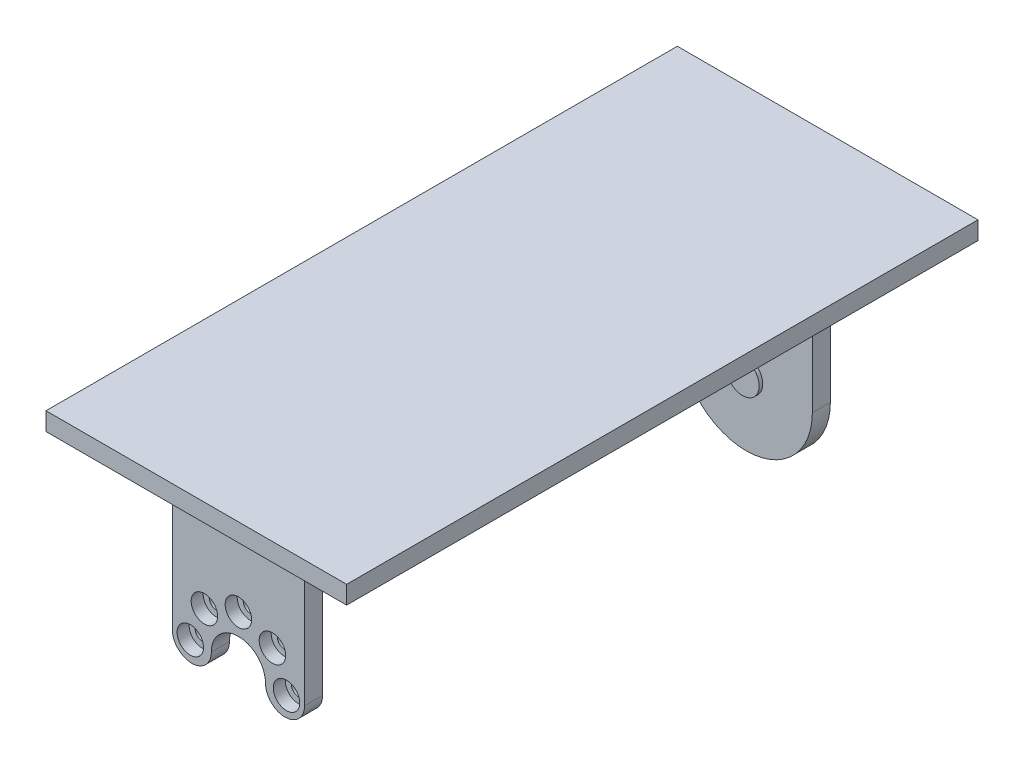
SolidWorks part; units mm, degrees
ref_plane "Plano frontal" through (0, 0, 0) normal (0, 0, 1) x (1, 0, 0)
ref_plane "Plano superior" through (0, 0, 0) normal (0, 1, 0) x (1, 0, 0)
ref_plane "Plano direito" through (0, 0, 0) normal (1, 0, 0) x (0, 0, -1)
other "Centro da massa"
sketch "Esboço1" plane through (0, 0, 0) normal (0, 0, 1) x (1, 0, 0)
  line L0 (11, 0) -> (11, 25)
  line L1 (11, 25) -> (-11, 25)
  line L2 (-11, 25) -> (-11, 0)
  arc A3 (11, 0) -> (4.5, 0) centre (7.75, 0) cw
  arc A8 (4.5, 0) -> (-4.5, 0) centre (0, 0) ccw
  arc A10 (-4.5, 0) -> (-11, 0) centre (-7.75, 0) cw
  dimension "D1" = 25
extrude "Ressalto-extrusão1" add sketch "Esboço1" along normal blind 3
sketch "Esboço2" plane through (0, 25, 0) normal (0, 1, 0) x (1, 0, 0)
  line L1 (-25, -10) -> (25, -10)
  line L2 (-25, -10) -> (-25, 95)
  line L3 (-25, 95) -> (25, 95)
  line L4 (25, -10) -> (25, 95)
  line L5 (11, -3) -> (-11, -3) construction
  point P7 (0, -3)
  point P8 (0, -10)
  dimension "D1" = 105
  dimension "D2" = 50
  dimension "D3" = 7
extrude "Ressalto-extrusão2" add sketch "Esboço2" along normal blind 3
ref_plane "Plano1" through (0, 0, -81.45) normal (0, 0, -1) x (-1, 0, 0)
sketch "Esboço3" plane through (0, 0, -81.45) normal (0, 0, -1) x (-1, 0, 0)
  line L1 (-11, 0) -> (-11, 25)
  line L2 (-11, 25) -> (11, 25)
  line L3 (11, 25) -> (11, 0)
  arc A0 (-11, 0) -> (11, 0) centre (0, 0) ccw
  dimension "D1" = 22
extrude "Ressalto-extrusão3" add sketch "Esboço3" along normal blind 3
hole_wizard "Rebaixo para SHCS M21" positions "Esboço4" profile "Esboço5" counterbore size "M2" standard "Ansi Metric" end condition up to next
sketch "Esboço4" plane through (0, 0, 3) normal (0, 0, 1) x (1, 0, 0)
  arc A0 (8.8, 0) -> (7.2, 0) centre (8, 0) ccw construction
  point P0 (8, 0)
sketch "Esboço5" plane through (8, 0, 3) normal (1, 0, 0) x (0, -1, 0)
  line L0 (0, 0) -> (0, 3)
  line L1 (0, 3) -> (1.2, 3)
  line L3 (1.2, 3) -> (1.2, 2)
  line L4 (1.2, 2) -> (2.2, 2)
  line L5 (2.2, 2) -> (2.2, 0)
  line L7 (2.2, 0) -> (0, 0)
  line L11 (0, -6.35) -> (0, 107.95) construction
  dimension "Thru Hole Dia." = 2.4
  dimension "Thru Hole Depth" = 3
  dimension "C'Bore Dia." = 4.4
  dimension "C'Bore Depth" = 2
pattern_circular "PadrãoCircular1" count 5 over 180 about axis through (0, 0, 3) along (0, 0, -1) of "Rebaixo para SHCS M21" reverse direction yes
sketch "Esboço6" plane through (0, 0, 0) normal (1, 0, 0) x (0, 0, -1)
  line L0 (-10, 25) -> (-3, 25) construction
  line L3 (-3, 25) -> (-3, 18) construction
  line L4 (-3, 0) -> (-3, 25) construction
  line L5 (-3, 18) -> (-10, 25)
rib "Nervura1" sketch "Esboço6" sketch "Esboço6" thickness 15 extrusion direction parallel to sketch draft on no parameters "D1"=15
sketch "Esboço7" plane through (0, 0, 3) normal (0, 0, 1) x (1, 0, 0)
  line L0 (-7.5, 25) -> (7.5, 25) construction
  line L1 (-5, 25) -> (5, 25)
  line L2 (-5, 25) -> (-5, 18)
  line L3 (-5, 18) -> (5, 18)
  line L4 (5, 25) -> (5, 18)
  line L5 (7.5, 18) -> (-7.5, 18) construction
  point P8 (0, 18)
  point P9 (0, 18)
  dimension "D1" = 10
extrude "Corte-extrusão1" cut sketch "Esboço7" along normal up to surface (7 mm away) up to face at (0, 21.5, 6.5)
sketch "Esboço8" plane through (0, 0, 0) normal (1, 0, 0) x (0, 0, -1)
  line L0 (0, 18) -> (7, 25)
  line L1 (0, 0) -> (0, 25) construction
  line L2 (-10, 25) -> (95, 25) construction
  line L5 (-10, 25) -> (-3, 18) construction
rib "Nervura7" sketch "Esboço8" sketch "Esboço8" thickness 15 extrusion direction parallel to sketch draft on no parameters "D1"=15
sketch "Esboço9" plane through (0, 0, 0) normal (0, 0, -1) x (-1, 0, 0)
  line L0 (-7.5, 18) -> (7.5, 18) construction
  line L1 (-5, 18) -> (5, 18)
  line L2 (-5, 18) -> (-5, 25)
  line L3 (-5, 25) -> (5, 25)
  line L4 (5, 18) -> (5, 25)
  line L5 (-11, 25) -> (-7.5, 25) construction
  point P8 (0, 18)
  point P9 (0, 18)
  dimension "D1" = 10
extrude "Corte-extrusão2" cut sketch "Esboço9" along normal up to surface up to face at (0, 21.5, -3.5)
pattern_linear "Padrão linear1" count 2 spacing 84.45 along (0, 0, -1) of "Nervura1", "Nervura7", "Corte-extrusão2", "Corte-extrusão1"
sketch "Esboço10" plane through (0, 0, -81.45) normal (0, 0, 1) x (1, 0, 0)
  circle A0 centre (0, 0) radius 2.75
  circle A2 centre (0, 0) radius 3.25 construction
  dimension "D1" = 0.5
extrude "Ressalto-extrusão4" add sketch "Esboço10" along normal offset from surface (0.6 mm away) 0.25 contours A0
